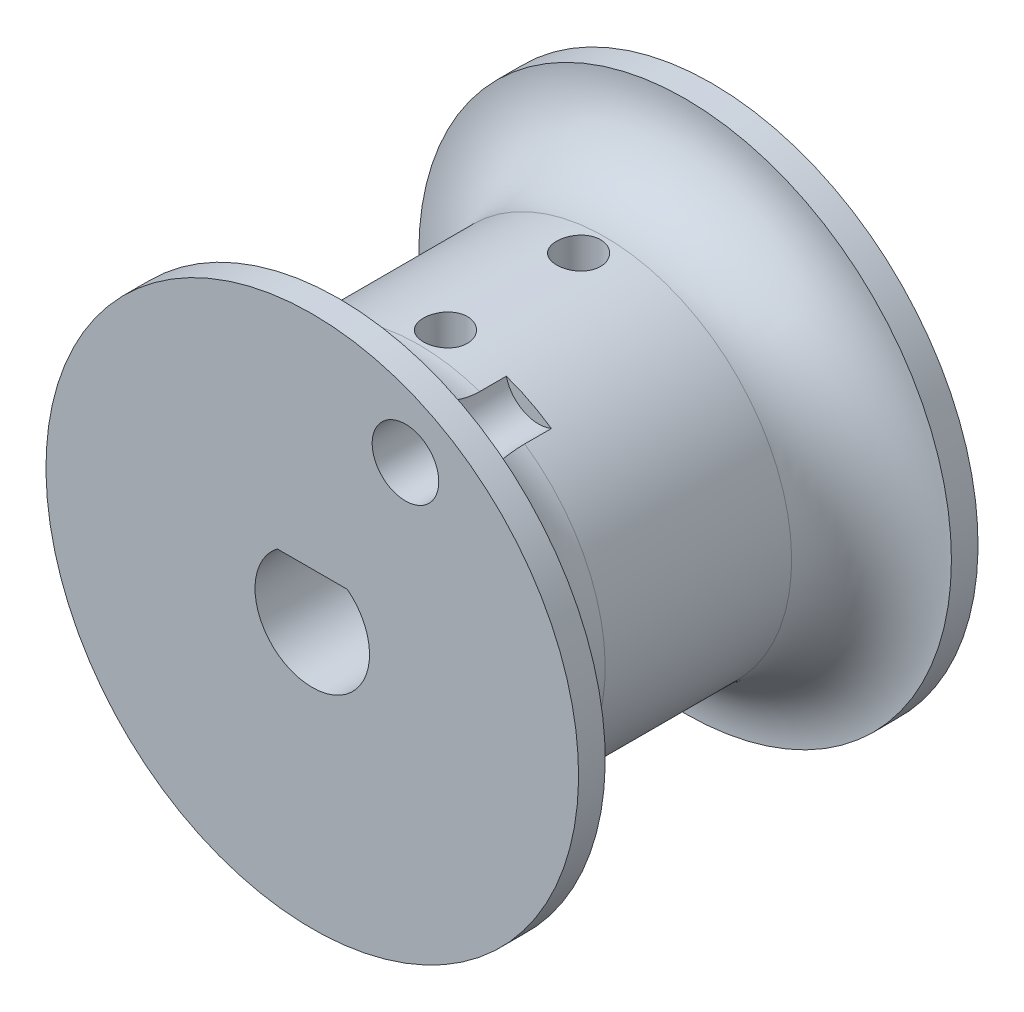
SolidWorks part; units mm, degrees
ref_plane "Front Plane" through (0, 0, 0) normal (0, 0, 1) x (1, 0, 0)
ref_plane "Top Plane" through (0, 0, 0) normal (0, 1, 0) x (1, 0, 0)
ref_plane "Right Plane" through (0, 0, 0) normal (1, 0, 0) x (0, 0, -1)
sketch "Sketch1" plane through (0, 0, 0) normal (1, 0, 0) x (0, 0, -1)
  line L0 (0, 0) -> (0, 14)
  line L1 (0, 14) -> (13, 14)
  line L2 (13, 14) -> (13, 20)
  line L3 (13, 20) -> (15, 20)
  line L4 (15, 20) -> (15, 0)
  line L5 (15, 0) -> (0, 0)
  dimension "D1" = 15
  dimension "D2" = 20
  dimension "D3" = 14
  dimension "D4" = 2
revolve "Revolve1" add sketch "Sketch1" angle 360 about L5
mirror "Mirror1" about plane through (0, 0, 0) normal (0, 0, 1) of "Revolve1"
sketch "Sketch2" plane through (0, 0, 15) normal (0, 0, 1) x (1, 0, 0)
  line L0 (-2.6325, 3.4) -> (2.6325, 3.4)
  arc A2 (-2.6325, 3.4) -> (2.6325, 3.4) centre (0, 0) ccw
  arc A3 (2.6325, 3.4) -> (-2.6325, 3.4) centre (0, 0) ccw construction
  point P1 (0, -4.3)
  dimension "D1" = 8.6
  dimension "D2" = 7.7
extrude "Cut-Extrude1" cut sketch "Sketch2" against normal through all
hole_wizard "Tap Drill for M4x0.7 Tap1" positions "Sketch4" profile "Sketch5" hole size "M4x0.7" standard "ANSI Metric" end condition through all
sketch "Sketch4" plane through (0, 0, 0) normal (0, 1, 0) x (1, 0, 0)
  line L0 (0, -5) -> (0, 0) construction
  line L1 (0, 0) -> (0, 5) construction
  point P0 (0, 5)
  point P2 (0, -5)
  dimension "D1" = 5
sketch "Sketch5" plane through (0, 0, -5) normal (1, 0, 0) x (0, 0, -1)
  line L0 (0, 0) -> (0, 20)
  line L1 (0, 20) -> (1.65, 20)
  line L2 (1.65, 20) -> (1.65, 0)
  line L5 (1.65, 0) -> (0, 0)
  line L11 (0, -6.35) -> (0, 107.95) construction
  dimension "Thru Hole Dia." = 3.3
  dimension "Thru Hole Depth" = 20
fillet "2" radius 6 2 edges at (0, 14, 13) (0, 14, -13)
sketch "Sketch6" plane through (0, 0, 15) normal (0, 0, 1) x (1, 0, 0)
  circle A0 centre (7, 13.8293) radius 2.5
  circle A1 centre (0, 0) radius 20 construction
  dimension "D1" = 5
  dimension "D2" = 15.5
  dimension "D3" = 7
extrude "Cut-Extrude2" cut sketch "Sketch6" against normal blind 10
